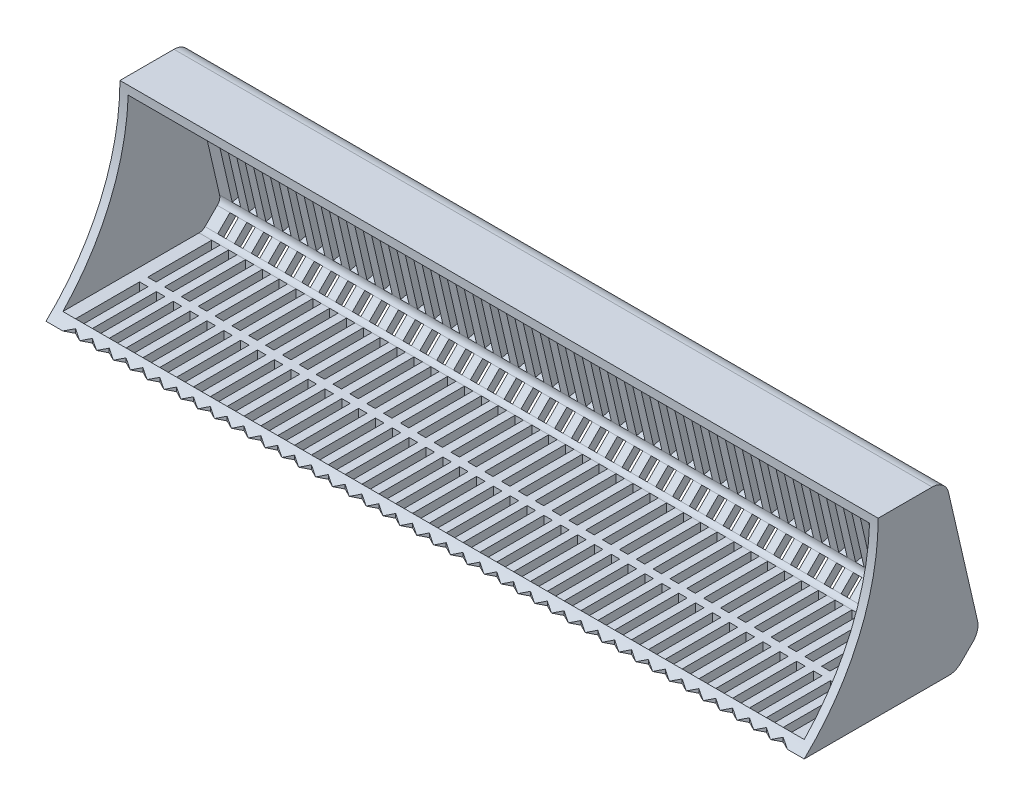
SolidWorks part; units mm, degrees
ref_plane "Front Plane" through (0, 0, 0) normal (0, 0, 1) x (1, 0, 0)
ref_plane "Top Plane" through (0, 0, 0) normal (0, 1, 0) x (1, 0, 0)
ref_plane "Right Plane" through (0, 0, 0) normal (1, 0, 0) x (0, 0, -1)
sketch "Sketch1" plane through (0, 0, 0) normal (1, 0, 0) x (0, 0, -1)
  line L0 (-45, 0) -> (45, 0)
  line L1 (45, 0) -> (59.1421, 14.1421)
  line L2 (59.1421, 14.1421) -> (38.8965, 101.8354)
  line L3 (38.8965, 101.8354) -> (-1.1035, 101.8354)
  arc A1 (-1.1035, 101.8354) -> (-45, 0) centre (-141.1756, 101.8354) cw
  dimension "D1" = 90
  dimension "D2" = 20
  dimension "D3" = 90
  dimension "D4" = 122
  dimension "D5" = 135
  dimension "D6" = 40
extrude "Boss-Extrude1" add sketch "Sketch1" along normal mid plane 450 contours L0 L1 L2 L3 A1
fillet "Fillet2" radius 10 3 edges at (0, 101.8354, -38.8965) (0, 14.1421, -59.1421) (0, 0, -45)
shell "Shell2" thickness 5
sketch "Sketch2" plane through (0, 5, 0) normal (0, 1, 0) x (1, 0, 0)
  line L0 (-220, 40.8579) -> (220, 40.8579) construction
  line L1 (-2.5, 40.8579) -> (2.5, 40.8579)
  line L2 (-2.5, 40.8579) -> (-2.5, 2.8579)
  line L3 (-2.5, 2.8579) -> (2.5, 2.8579)
  line L4 (2.5, 40.8579) -> (2.5, 2.8579)
  line L5 (220, -39.9674) -> (-220, -39.9674) construction
  line L6 (-2.5, -1.9674) -> (2.5, -1.9674)
  line L7 (-2.5, -1.9674) -> (-2.5, -39.9674)
  line L8 (-2.5, -39.9674) -> (2.5, -39.9674)
  line L9 (2.5, -1.9674) -> (2.5, -39.9674)
  line L10 (225, -45) -> (-225, -45) construction
  line L11 (225, -45) -> (-225, -45)
  line L13 (-2.5, -45) -> (2.5, -45)
  line L15 (0, -42.4674) -> (5, -45)
  line L16 (5, -45) -> (-5, -45)
  line L17 (-5, -45) -> (0, -42.4674)
  line L18 (0, -39.9674) -> (0, -45) construction
  dimension "D1" = 2.5
  dimension "D2" = 2.5
  dimension "D3" = 38
  dimension "D4" = 2.5
  dimension "D5" = 10
extrude "Cut-Extrude1" cut sketch "Sketch2" against normal through all
pattern_linear "LPattern1" count 22 spacing 10 along (1, 0, 0) count 22 spacing 10 along (-1, 0, 0) of "Cut-Extrude1"
sketch "Sketch3" plane through (0, -18.9645, -18.9645) normal (0, 0.7071, 0.7071) x (1, 0, 0)
  line L0 (-220, 46.2767) -> (220, 46.2767) construction
  line L1 (-2.5, 46.2767) -> (2.5, 46.2767)
  line L2 (-2.5, 46.2767) -> (-2.5, 35.9619)
  line L3 (-2.5, 35.9619) -> (2.5, 35.9619)
  line L4 (2.5, 46.2767) -> (2.5, 35.9619)
  line L5 (220, 35.9619) -> (-220, 35.9619) construction
  line L6 (0, 0) -> (0, 35.9619) construction
  dimension "D1" = 5
extrude "Cut-Extrude2" cut sketch "Sketch3" against normal blind 10
pattern_linear "LPattern2" count 22 spacing 10 along (1, 0, 0) count 22 spacing 10 along (-1, 0, 0) of "Cut-Extrude2"
sketch "Sketch4" plane through (0, 12.554, -54.3773) normal (0, -0.225, 0.9744) x (1, 0, 0)
  line L0 (220, 6.0187) -> (-220, 6.0187) construction
  line L1 (-2.5, 6.0187) -> (2.5, 6.0187)
  line L2 (-2.5, 6.0187) -> (-2.5, 41.77)
  line L3 (-2.5, 41.77) -> (2.5, 41.77)
  line L4 (2.5, 6.0187) -> (2.5, 41.77)
  line L5 (-220, 82.5212) -> (220, 82.5212) construction
  line L6 (-2.5, 82.5212) -> (2.5, 82.5212)
  line L7 (-2.5, 82.5212) -> (-2.5, 46.77)
  line L8 (-2.5, 46.77) -> (2.5, 46.77)
  line L9 (2.5, 82.5212) -> (2.5, 46.77)
  line L10 (0, 0) -> (0, 6.0187) construction
  dimension "D1" = 5
  dimension "D2" = 5
extrude "Cut-Extrude3" cut sketch "Sketch4" against normal through all
pattern_linear "LPattern3" count 22 spacing 10 along (1, 0, 0) count 22 spacing 10 along (-1, 0, 0) of "Cut-Extrude3"
